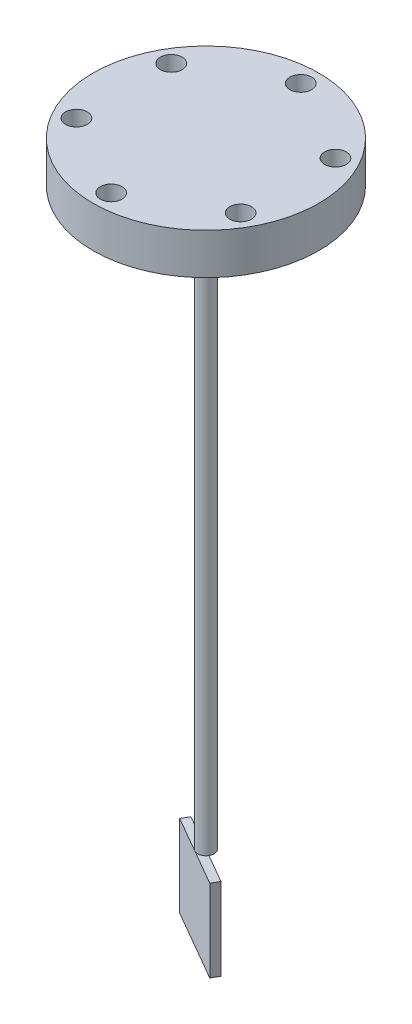
SolidWorks part; units mm, degrees
note: '?' marks a value the reader was unsure of.
ref_plane "Front Plane" through (0, 0, 0) normal (0, 0, 1) x (1, 0, 0)
ref_plane "Top Plane" through (0, 0, 0) normal (0, 1, 0) x (1, 0, 0)
ref_plane "Right Plane" through (0, 0, 0) normal (1, 0, 0) x (0, 0, -1)
sketch "Sketch1" plane through (0, 0, 0) normal (0, 1, 0) x (1, 0, 0)
  circle A0 centre (0, 0) radius 34.925
  dimension "D1" = 69.85
extrude "Extrude1" add sketch "Sketch1" along normal blind 12.7
sketch "Sketch2" plane through (0, 0, 0) normal (0, 1, 0) x (1, 0, 0)
  circle A0 centre (0, 0) radius 17.399
  dimension "D1" = 34.798
extrude "Cut-Extrude1" [suppressed] cut sketch "Sketch2" along normal through all
sketch "Sketch3" plane through (0, 0, 0) normal (0, 1, 0) x (1, 0, 0)
  circle A0 centre (0, 29.337) radius 3.3655
  dimension "D1" = 6.731
  dimension "D2" = 29.337
extrude "Cut-Extrude2" cut sketch "Sketch3" along normal blind 12.7
ref_axis "Axis1" through (0, 35.8582, 0) along (0, -1, 0)?
pattern_circular "CirPattern1" count 6 over 360 about axis through (0, 0, 0) along (0, 1, 0) of "Cut-Extrude2"
sketch "Sketch4" plane through (0, 0, 0) normal (0, 1, 0) x (1, 0, 0)
  line L0 (0, 0) -> (0, 16.8619)
ref_plane "Plane1" through (0, 12.7, 0) normal (0, 1, 0) x (-1, 0, 0)
ref_plane "Plane2" through (0, 0, 0) normal (0, -1, 0) x (1, 0, 0)
sketch "Sketch8" plane through (0, 0, 0) normal (0, -1, 0) x (1, 0, 0)
  circle A0 centre (0, 0) radius 2.54
extrude "Extrude3" add sketch "Sketch8" along normal blind 177.8
ref_axis "Axis2" through (-25.4066, 12.7, -14.6685) along (0, -1, 0)?
sketch "Sketch9" plane through (0, 12.7, 0) normal (0, 1, 0) x (-1, 0, 0)
  line L0 (0, 0) -> (25.4066, -14.6685)
ref_plane "Plane3" through (-25.4066, 12.7, -14.6685) normal (-0.866, 0, -0.5) x (-0.5, 0, 0.866)
sketch "Sketch10" plane through (-25.4066, 12.7, -14.6685) normal (-0.866, 0, -0.5) x (-0.5, 0, 0.866)
  line L0 (0, 0) -> (0, -190.5)
  line L1 (38.4175, 0) -> (-38.4175, 0) construction
  line L2 (-2.54, -190.5) -> (2.54, -190.5) construction
ref_plane "Plane4" through (0, -177.8, 0) normal (0, -1, 0) x (1, 0, 0)
sketch "Sketch12" plane through (0, -177.8, 0) normal (0, -1, 0) x (1, 0, 0)
  line L0 (0, 0) -> (-10.9985, -6.35)
  line L1 (0, 0) -> (-25.4066, -14.6685) construction
  line L2 (0, 0) -> (10.9985, 6.35)
  dimension "D1" = 12.7
  dimension "D2" = 12.7
extrude "Extrude-Thin1" add sketch "Sketch12" along normal blind 25.4 thin
